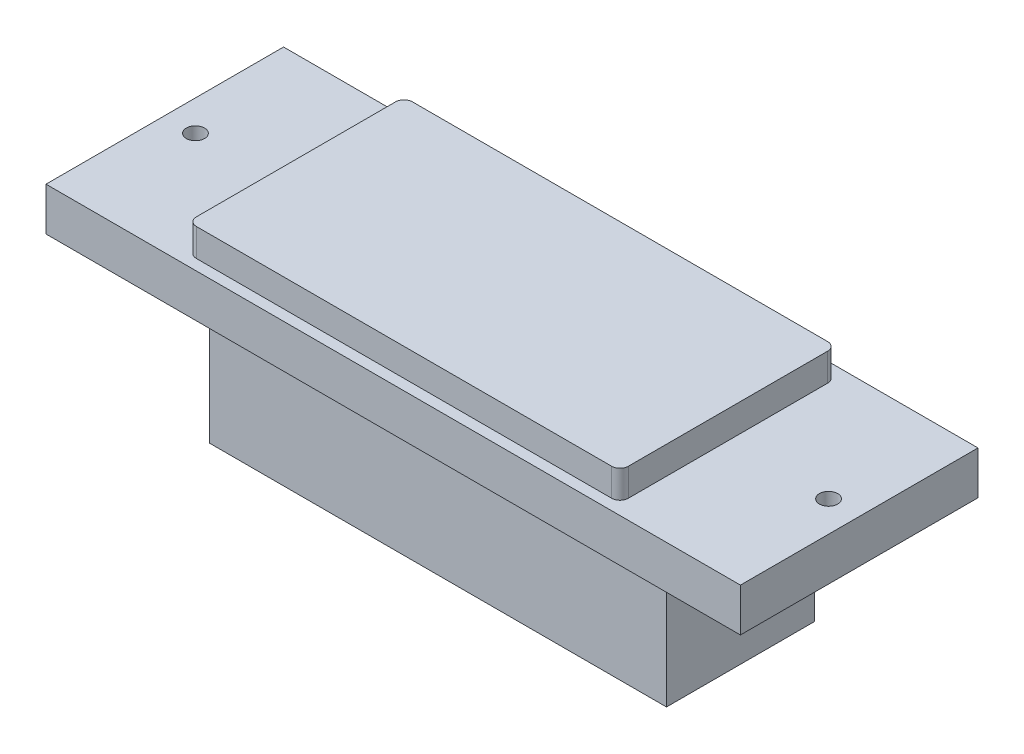
SolidWorks part; units mm, degrees
ref_plane "Front Plane" through (0, 0, 0) normal (0, 0, 1) x (1, 0, 0)
ref_plane "Top Plane" through (0, 0, 0) normal (0, 1, 0) x (1, 0, 0)
ref_plane "Right Plane" through (0, 0, 0) normal (1, 0, 0) x (0, 0, -1)
sketch "Sketch1" plane through (0, 0, 0) normal (0, 1, 0) x (1, 0, 0)
  line L1 (-33.02, 16.51) -> (33.02, 16.51)
  line L2 (-33.02, 16.51) -> (-33.02, -16.51)
  line L3 (-33.02, -16.51) -> (33.02, -16.51)
  line L4 (33.02, 16.51) -> (33.02, -16.51)
  line L5 (-33.02, 16.51) -> (33.02, -16.51) construction
  line L6 (-33.02, -16.51) -> (33.02, 16.51) construction
  point P0 (0, 0)
  dimension "D1" = 66.04
  dimension "D2" = 33.02
extrude "Boss-Extrude1" add sketch "Sketch1" along normal blind 4.2418
fillet "Fillet1" radius 1.27 4 edges at (33.02, 2.1209, 16.51) (33.02, 2.1209, -16.51) (-33.02, 2.1209, -16.51) (-33.02, 2.1209, 16.51)
sketch "Sketch2" plane through (0, 0, 0) normal (0, -1, 0) x (1, 0, 0)
  line L1 (53.086, 18.161) -> (-53.086, 18.161)
  line L2 (53.086, 18.161) -> (53.086, -18.161)
  line L3 (53.086, -18.161) -> (-53.086, -18.161)
  line L4 (-53.086, 18.161) -> (-53.086, -18.161)
  line L5 (53.086, 18.161) -> (-53.086, -18.161) construction
  line L6 (53.086, -18.161) -> (-53.086, 18.161) construction
  point P0 (0, 0)
  dimension "D1" = 36.322
  dimension "D2" = 106.172
extrude "Boss-Extrude2" add sketch "Sketch2" along normal blind 6.604
sketch "Sketch3" plane through (0, 0, 0) normal (0, 1, 0) x (1, 0, 0)
  line L0 (-53.086, 0) -> (-48.3997, 0) construction
  line L1 (-53.086, -18.161) -> (-53.086, 18.161) construction
  line L2 (-48.3997, 0) -> (48.3997, 0) construction
  line L3 (48.3997, 0) -> (53.086, 0) construction
  line L4 (53.086, 18.161) -> (53.086, -18.161) construction
  dimension "D1" = 96.7994
hole_wizard "#3 Clearance Hole1" positions "Sketch4" profile "Sketch5" hole size "#3" standard "ANSI Inch" end condition through all
sketch "Sketch4" plane through (0, 0, 0) normal (0, 1, 0) x (1, 0, 0)
  point P0 (-48.3997, 0)
  point P3 (48.3997, 0)
sketch "Sketch5" plane through (-48.3997, 0, 0) normal (1, 0, 0) x (0, 0, 1)
  line L0 (0, 0) -> (0, 6.604)
  line L1 (0, 6.604) -> (1.397, 6.604)
  line L2 (1.397, 6.604) -> (1.397, 0)
  line L5 (1.397, 0) -> (0, 0)
  line L11 (0, -6.35) -> (0, 107.95) construction
  dimension "Thru Hole Dia." = 2.794
  dimension "Thru Hole Depth" = 6.604
sketch "Sketch6" plane through (0, -6.604, 0) normal (0, -1, 0) x (1, 0, 0)
  line L1 (34.925, 11.303) -> (-34.925, 11.303)
  line L2 (34.925, 11.303) -> (34.925, -11.303)
  line L3 (34.925, -11.303) -> (-34.925, -11.303)
  line L4 (-34.925, 11.303) -> (-34.925, -11.303)
  line L5 (34.925, 11.303) -> (-34.925, -11.303) construction
  line L6 (34.925, -11.303) -> (-34.925, 11.303) construction
  point P0 (0, 0)
  dimension "D1" = 69.85
  dimension "D2" = 22.606
extrude "Boss-Extrude3" add sketch "Sketch6" along normal blind 22.0472
